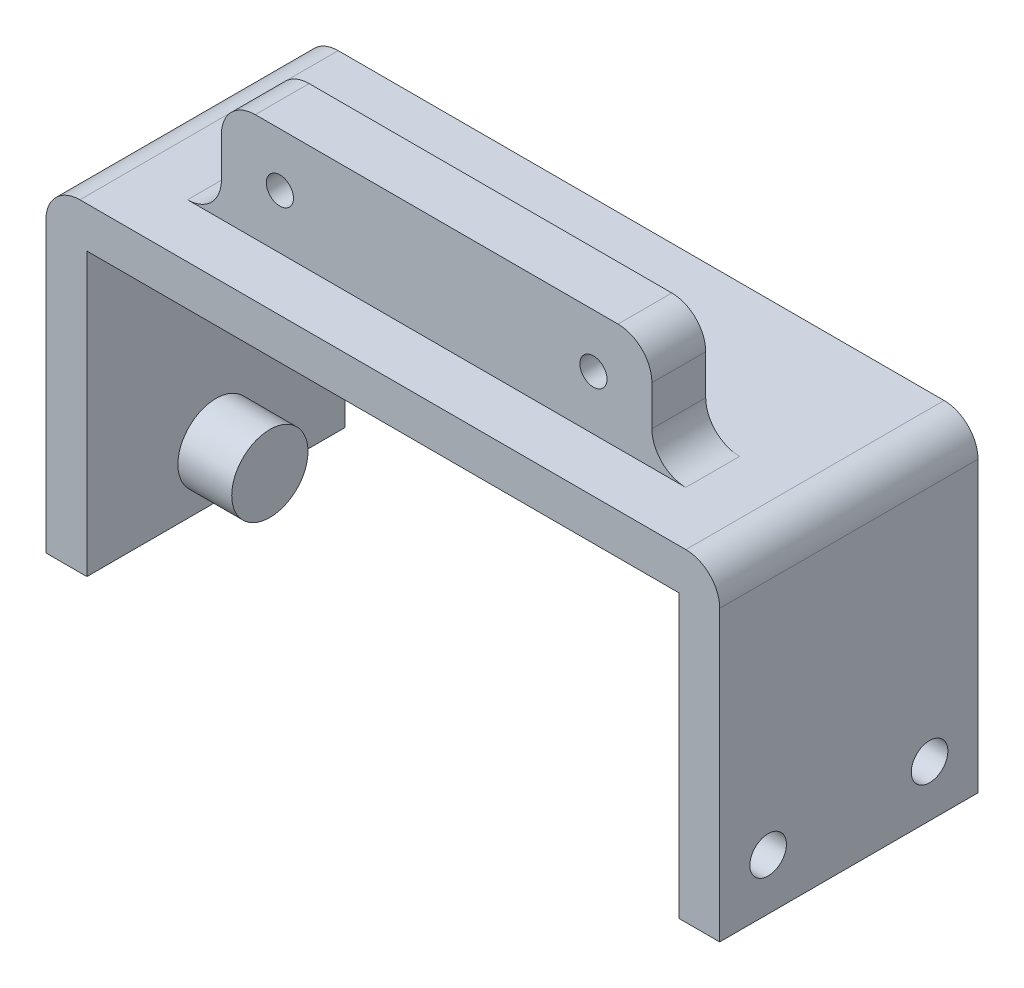
SolidWorks part; units mm, degrees
ref_plane "Front" through (0, 0, 0) normal (0, 0, 1) x (1, 0, 0)
ref_plane "Top" through (0, 0, 0) normal (0, 1, 0) x (1, 0, 0)
ref_plane "Right" through (0, 0, 0) normal (1, 0, 0) x (0, 0, -1)
sketch "Sketch2" plane through (0, 0, 0) normal (1, 0, 0) x (0, 0, -1)
  line L0 (15.24, 38.1) -> (15.24, 0) construction
  line L1 (0, 0) -> (30.48, 0)
  line L2 (0, 0) -> (0, 38.1)
  line L3 (0, 38.1) -> (30.48, 38.1)
  line L4 (30.48, 0) -> (30.48, 38.1)
  circle A0 centre (5.715, 6.05) radius 2.159
  circle A1 centre (24.765, 6.05) radius 2.159
  point P9 (15.24, 6.05)
  dimension "D2" = 4.318
  dimension "D1" = 30.48
  dimension "D3" = 9.525
  dimension "D5" = 38.1
extrude "Boss-Extrude1" add sketch "Sketch2" along normal blind 4.826
sketch "Sketch3" plane through (0, 0, 0) normal (-1, 0, 0) x (0, 0, 1)
  line L1 (-30.48, 38.1) -> (0, 38.1)
  line L2 (-30.48, 38.1) -> (-30.48, 33.274)
  line L3 (-30.48, 33.274) -> (0, 33.274)
  line L4 (0, 38.1) -> (0, 33.274)
  dimension "D1" = 4.826
extrude "Boss-Extrude2" add sketch "Sketch3" along normal blind 74.676
sketch "Sketch4" plane through (0, 33.274, 0) normal (0, -1, 0) x (1, 0, 0)
  line L0 (-74.676, -30.48) -> (0, -30.48) construction
  line L1 (-74.676, 0) -> (-69.85, 0)
  line L2 (-74.676, 0) -> (-74.676, -30.48)
  line L3 (-74.676, -30.48) -> (-69.85, -30.48)
  line L4 (-69.85, 0) -> (-69.85, -30.48)
  dimension "D1" = 4.826
extrude "Boss-Extrude4" add sketch "Sketch4" along normal blind 33.274
sketch "Sketch5" plane through (0, 38.1, 0) normal (0, 1, 0) x (1, 0, 0)
  line L0 (-34.925, 30.48) -> (-34.925, 0) construction
  line L1 (4.826, 30.48) -> (-74.676, 30.48) construction
  line L2 (4.826, 0) -> (-74.676, 0) construction
  line L4 (-60.325, 6.35) -> (-9.525, 6.35)
  line L5 (-60.325, 6.35) -> (-60.325, 12.7)
  line L6 (-60.325, 12.7) -> (-9.525, 12.7)
  line L7 (-9.525, 6.35) -> (-9.525, 12.7)
  point P10 (-9.525, 9.525)
  point P11 (-9.525, 0)
  point P12 (0, 0)
  dimension "D1" = 25.4
  dimension "D2" = 25.4
  dimension "D3" = 6.35
  dimension "D4" = 6.35
extrude "Boss-Extrude5" add sketch "Sketch5" along normal blind 12.7
sketch "Sketch6" plane through (0, 0, -12.7) normal (0, 0, -1) x (-1, 0, 0)
  line L5 (9.525, 50.8) -> (60.325, 50.8) construction
  line L6 (20.275, 50.9) -> (49.575, 50.9) construction
  line L7 (20.275, 50.9) -> (20.275, 38.1) construction
  line L8 (20.275, 38.1) -> (49.575, 38.1) construction
  line L9 (49.575, 50.9) -> (49.575, 38.1) construction
  circle A2 centre (16.425, 44.5) radius 1.6
  circle A3 centre (53.425, 44.5) radius 1.6
  point P4 (34.925, 50.9)
  point P7 (34.925, 50.8)
extrude "Cut-Extrude1" cut sketch "Sketch6" against normal up to next
fillet "Fillet2" radius 4 6 edges at (-74.676, 38.1, -15.24) (4.826, 38.1, -15.24) (-60.325, 50.8, -9.525) (-60.325, 38.1, -9.525) (-9.525, 38.1, -9.525) (-9.525, 50.8, -9.525)
sketch "Sketch7" plane through (-69.85, 0, 0) normal (1, 0, 0) x (0, 0, -1)
  line L0 (30.48, 0) -> (0, 0) construction
  line L1 (15.24, 33.274) -> (15.24, 0) construction
  line L2 (30.48, 33.274) -> (0, 33.274) construction
  circle A0 centre (15.24, 6.096) radius 4.5
  point P8 (0, 0)
  dimension "D1" = 6.096
  dimension "D2" = 9
extrude "Boss-Extrude6" add sketch "Sketch7" along normal blind 6.35
